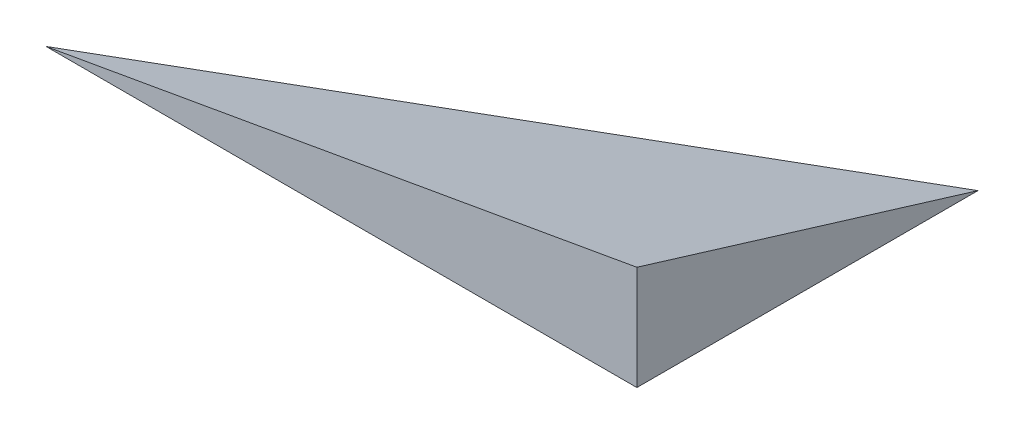
SolidWorks part; units mm, degrees
ref_plane "Front Plane" through (0, 0, 0) normal (0, 0, 1) x (1, 0, 0)
ref_plane "Top Plane" through (0, 0, 0) normal (0, 1, 0) x (1, 0, 0)
ref_plane "Right Plane" through (0, 0, 0) normal (1, 0, 0) x (0, 0, -1)
ref_axis "Axis1" through (0, 0, -202.9227) along (0, 0, 1)
ref_plane "Plane1" through (0, 0, 0) normal (-0.1736, 0.9848, 0) x (0, 0, 1)
sketch "Sketch1" plane through (0, 0, 0) normal (0, 0, 1) x (1, 0, 0)
  line L0 (0, 0) -> (270.8221, 47.7532)
  line L1 (169.5065, 29.8886) -> (-169.5065, -29.8886) construction
  line L2 (270.8221, 47.7532) -> (270.8221, 0)
  line L3 (55, 0) -> (-55, 0) construction
  line L9 (0, 0) -> (270.8221, 0)
  dimension "D1" = 275
sketch "Sketch3" plane through (0, 0, 0) normal (0, 1, 0) x (1, 0, 0)
  line L0 (270.8221, 0) -> (270.8221, 156.3592)
  line L1 (0, 0) -> (270.8221, 0) construction
  line L2 (-55, 0) -> (55, 0) construction
  line L3 (270.8221, 156.3592) -> (0, 0)
  line L4 (0, 0) -> (270.8221, 0)
  dimension "D2" = 30
loft "Loft1" add profiles "Sketch3", "Sketch1" connector at (270.8221, 0, -156.3592) connector at (270.8221, 47.7532, 0)
ref_plane "Plane2" [suppressed] through (0, 0, -270.8221) normal (0, 0, 1) x (1, 0, 0)
sketch "Sketch4" [suppressed] plane through (0, 0, -270.8221) normal (0, 0, 1) x (1, 0, 0)
  line L3 (-172.3414, 0) -> (-172.3414, -30.3884)
  line L7 (148.9577, 0) -> (-148.9577, 0) construction
  line L8 (-172.3414, -30.3884) -> (0, 0)
  line L9 (0, 0) -> (-172.3414, 0)
  line L13 (169.5065, 29.8886) -> (-169.5065, -29.8886) construction
  dimension "D1" = 175
sketch "Sketch5" [suppressed] plane through (0, 0, 0) normal (0, 1, 0) x (1, 0, 0)
  line L1 (-172.3414, 0) -> (-172.3414, 172.3414)
  line L2 (0, 172.3414) -> (-172.3414, 172.3414) construction
  line L3 (-172.3414, 0) -> (0, 172.3414)
  line L5 (-172.3414, 172.3414) -> (0, 172.3414) construction
  line L6 (0, -33.43) -> (0, 33.43) construction
  line L8 (-33.43, 172.3414) -> (33.43, 172.3414) construction
  line L11 (-172.3414, 172.3414) -> (0, 172.3414)
ref_axis "Axis2" through (0, -1.5249, 0) along (0, 1, 0)
sketch "Sketch6" [suppressed] plane through (0, 0, 0) normal (-0.1736, 0.9848, 0) x (0, 0, 1)
  line L0 (-270.8221, 0) -> (0, -175)
  line L1 (-270.8221, -175) -> (-270.8221, 0) construction
  line L2 (-270.8221, -175) -> (0, -175)
  line L3 (-270.8221, -175) -> (-270.8221, 0)
  line L4 (0, -26.2698) -> (0, 26.2698) construction
  line L6 (-202.9227, 0) -> (65.5473, 0) construction
  point P4 (0, 0)
  point P7 (0, 0)
  point P8 (-172.3414, -2.4986)
  point P9 (-172.3414, 0)
  point P10 (0, 0)
  point P11 (-172.3414, -2.6586)
  point P12 (0, 0)
  point P13 (-172.3414, -2.6586)
  point P14 (0, -175)
  point P19 (0, 0)
loft "Loft3" [suppressed] add profiles "Sketch6", "Sketch4"
sketch "Sketch7" [suppressed] plane through (0, 0, 0) normal (0, 1, 0) x (1, 0, 0)
  line L1 (0, 0) -> (270.8221, 0)
  line L2 (0, 0) -> (0, 270.8221)
  line L3 (0, 270.8221) -> (270.8221, 270.8221)
  line L4 (270.8221, 0) -> (270.8221, 270.8221)
extrude "Boss-Extrude1" [suppressed] add sketch "Sketch7" against normal blind 30
sketch "Sketch8" [suppressed] plane through (0, 0, 0) normal (-0.1736, 0.9848, 0) x (0, 0, 1)
  line L1 (0, -175) -> (-172.3414, -175)
  line L2 (0, -175) -> (0, 0)
  line L3 (0, 0) -> (-172.3414, 0)
  line L4 (-172.3414, -175) -> (-172.3414, 0)
extrude "Boss-Extrude3" [suppressed] add sketch "Sketch8" against normal up to surface up to face at (180.5481, 0, -52.1197)
